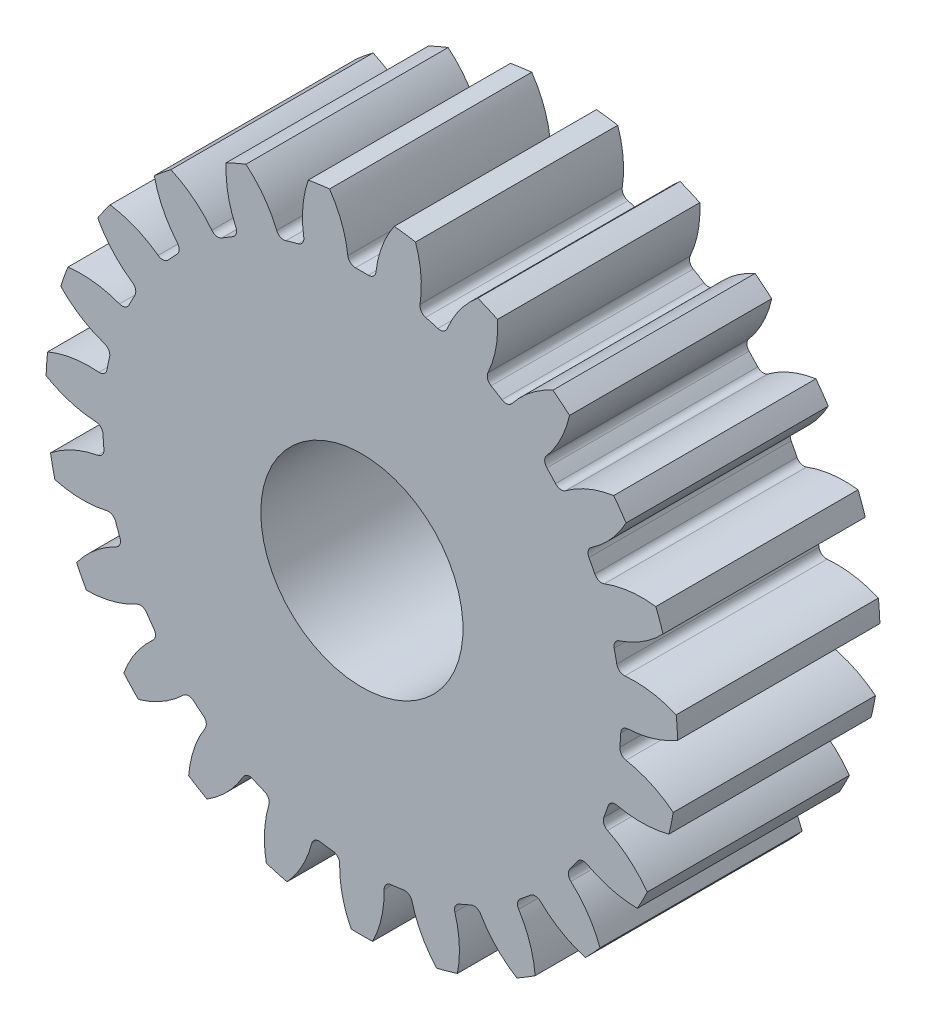
SolidWorks part; units mm, degrees
ref_plane "Front Plane" through (0, 0, 0) normal (0, 0, 1) x (1, 0, 0)
ref_plane "Top Plane" through (0, 0, 0) normal (0, 1, 0) x (1, 0, 0)
ref_plane "Right Plane" through (0, 0, 0) normal (1, 0, 0) x (0, 0, -1)
sketch "Sketch2" plane through (0, 0, 0) normal (0, 0, 1) x (1, 0, 0)
  circle A0 centre (0, 0) radius 14.375 construction
  circle A1 centre (0, 0) radius 15.625
  dimension "D1" = 28.75
  dimension "D2" = 31.25
extrude "Boss-Extrude1" add sketch "Sketch2" along normal mid plane 10 contours A1
sketch "Sketch3" plane through (0, 0, 0) normal (0, 0, 1) x (1, 0, 0)
  line L0 (0, 15.625) -> (0, 0) construction
  line L1 (0, 0) -> (4.2156, 15.0456) construction
  line L2 (0, 0) -> (2.1276, 15.4795) construction
  line L3 (-0.6666, 12.7951) -> (0, 0) construction
  line L4 (-0.981, 14.3415) -> (0.981, 14.3415) construction
  line L5 (0.981, 14.3415) -> (2.9247, 14.0743) construction
  line L6 (-1.4245, 15.5599) -> (0, 11.6463) construction
  circle A0 centre (0, 0) radius 13.125 construction
  arc A1 (0.6666, 12.7951) -> (-0.6666, 12.7951) centre (0, 0) ccw
  circle A2 centre (0, 0) radius 15.625 construction
  circle A3 centre (0, 0) radius 14.375 construction
  arc A4 (-1.6005, 15.5428) -> (-0.6666, 12.7951) centre (-5.9918, 12.5177) cw
  arc A5 (1.6005, 15.5428) -> (0.6666, 12.7951) centre (5.9918, 12.5177) ccw
  arc A6 (1.6005, 15.5428) -> (-1.6005, 15.5428) centre (0, 0) ccw
  dimension "D4" = 28.75
  dimension "D1" = 15.652
  dimension "D2" = 2.5
  dimension "D3" = 2.8125
  dimension "D5" = 20
extrude "Cut-Extrude1" cut sketch "Sketch3" against normal through all both and the other way through all
fillet "Fillet1" radius 0.375 2 edges at (0.6666, 12.7951, 0) (-0.6666, 12.7951, 0)
ref_axis "Axis1" through (0, 0, -11) along (0, 0, 1)
pattern_circular "CirPattern1" count 23 over 360 about axis through (0, 0, -11) along (0, 0, 1) of "Cut-Extrude1", "Fillet1"
sketch "Sketch4" plane through (0, 0, -5) normal (0, 0, -1) x (-1, 0, 0)
  circle A0 centre (0, 0) radius 5
  dimension "D1" = 10
extrude "Cut-Extrude3" cut sketch "Sketch4" against normal blind 10
equation "\"Module\" = 1.25mm"
equation "\"Number of teeth\"= 23"
equation "\"pressure angle\"= 20"
equation "\"D1@Sketch2\"=\"Module\"*\"Number of teeth\""
equation "\"D2@Sketch2\"=(\"Number of teeth\"+2) *\"Module\""
equation "\"D1@Sketch3\"=360 /\"Number of teeth\""
equation "\"D2@Sketch3\"=\"Module\"*2"
equation "\"D3@Sketch3\"=\"Module\" *if( \"Module\"=> 1.25,2.25,2.4)"
equation "\"D5@Sketch3\"=\"pressure angle\""
equation "\"D4@Sketch3\"=\"Module\"*\"Number of teeth\""
equation "\"D1@CirPattern1\"=\"Number of teeth\""
equation "\"D1@Fillet1\"=0.3 *\"Module\""
